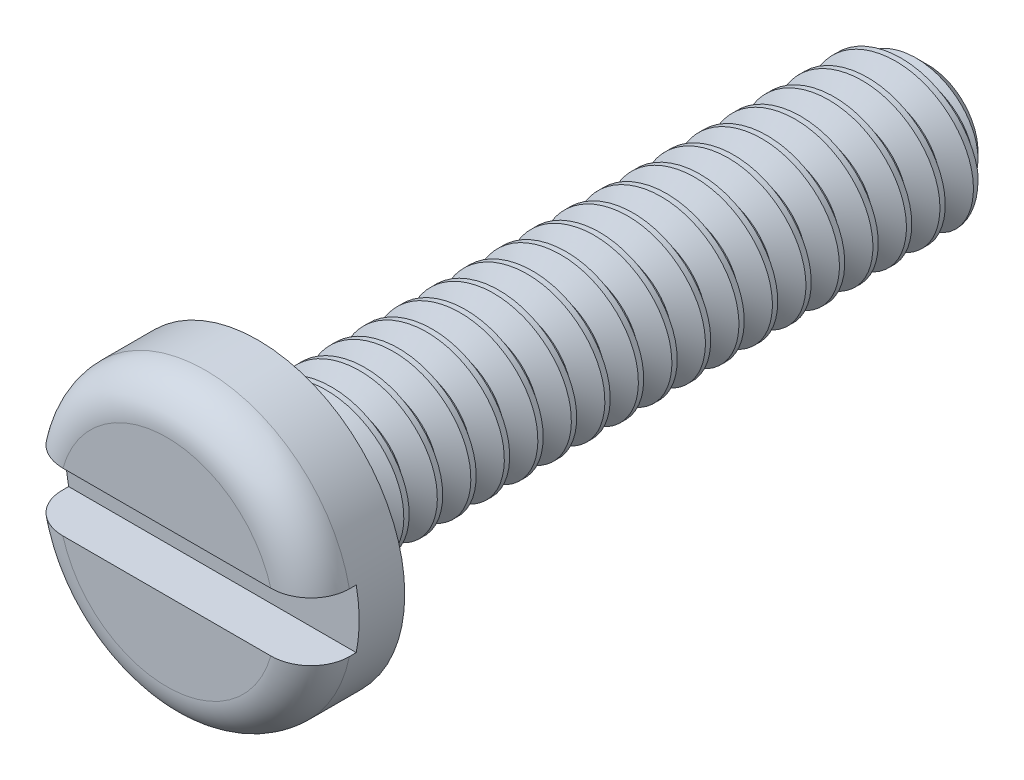
SolidWorks part; units mm, degrees
ref_plane "Front" through (0, 0, 0) normal (0, 0, 1) x (1, 0, 0)
ref_plane "Top" through (0, 0, 0) normal (0, 1, 0) x (1, 0, 0)
ref_plane "Right" through (0, 0, 0) normal (1, 0, 0) x (0, 0, -1)
sketch "Sketch1" plane through (0, 0, 0) normal (0, 0, 1) x (1, 0, 0)
  circle A0 centre (0, 0) radius 2.7813
  dimension "Head Dia" = 5.5626
extrude "Extrude3" add sketch "Sketch1" along normal blind 1.7272
sketch "Sketch11" plane through (0, 0, 0) normal (1, 0, 0) x (0, 0, -1)
  line L0 (0, 0) -> (-1.9812, 0) construction
  line L1 (-1.7272, 2.0472) -> (-1.7272, 0)
  line L4 (-1.7272, 2.7813) -> (-1.7272, -2.7813) construction
  line L5 (-1.9812, 2.8926) -> (0, 2.8926)
  line L7 (0, 2.8926) -> (0, 2.7813)
  line L8 (-0.9931, 2.7813) -> (0, 2.7813)
  line L9 (0, -2.7813) -> (0, 2.7813) construction
  line L11 (0, 2.7813) -> (-1.7272, 2.7813) construction
  line L13 (-1.7272, 0) -> (-1.9812, 0)
  line L14 (-1.9812, 0) -> (-1.9812, 2.8926)
  arc A2 (-1.7272, 2.0472) -> (-0.9931, 2.7813) centre (-0.9931, 2.0472) cw
  dimension "D4" = 0.7341
  dimension "D3" = 0.254
  dimension "D5" = 0.1113
revolve "Cut-Revolve3" cut sketch "Sketch11" angle 360 about L0
sketch "Sketch4" plane through (0, 0, 0) normal (1, 0, 0) x (0, 0, -1)
  line L0 (0, 0) -> (12.7, 0)
  line L3 (12.7, 0) -> (12.7, 1.4224)
  line L4 (12.7, 1.4224) -> (0, 1.4224)
  line L6 (0, 1.4224) -> (0, 0)
  line L9 (12.7, 1.4224) -> (12.7, -1.4224) construction
  dimension "length" = 12.7
  dimension "dia" = 2.8448
revolve "Revolve1" add sketch "Sketch4" angle 360 about L0
sketch "Sketch13" plane through (0, 0, -12.7) normal (0, 0, -1) x (-1, 0, 0)
  circle A2 centre (0, 0) radius 1.4224
curve "Helix/Spiral1" pitch 0.635 height 14.4272 turns 22.72
chamfer "Chamfer2" distance 0.4763 angle 45 1 edges at (1.4224, 0, -12.7)
sketch "Sketch14" plane through (0, 0, 0) normal (1, 0, 0) x (0, 0, -1)
  line L0 (12.7, 1.4422) -> (13.2556, 1.4422)
  line L1 (13.2556, 1.4422) -> (13.0175, 1.0127)
  line L2 (13.0175, 1.0127) -> (12.9381, 1.0127)
  line L3 (12.9381, 1.0127) -> (12.7, 1.4422)
  line L4 (12.8191, 1.2274) -> (13.1366, 1.2274) construction
  dimension "D1" = 0.0794
  dimension "D2" = 58
  dimension "D3" = 0.3175
  dimension "D4" = 0.0198
sweep "Cut-Sweep1" cut profiles "Sketch14" path "Helix/Spiral1"
ref_plane "Plane1" through (0, 0, 25.4) normal (0, 0, -1) x (-1, 0, 0)
sketch "Sketch29" [suppressed] plane through (0, 0, 28.575) normal (0, 0, -1) x (-1, 0, 0)
  circle A0 centre (0, 0) radius 1.7526 construction
  circle A1 centre (0, 0) radius 1.7526
  point P3 (0, -1.7526)
  point P4 (0, 1.7526)
extrude "Extrude11" [suppressed] add sketch "Sketch29" against normal up to surface (28.575 mm away)
sketch "Sketch26" plane through (0, 0, 0) normal (0, 0, 1) x (1, 0, 0)
  circle A1 centre (0, 0) radius 0.5461
  dimension "D1" = 1.0922
extrude "Extrude13" add sketch "Sketch26" along normal up to surface (1.7272 mm away) up to face at (0, 2.0472, 1.7272)
sketch "Sketch31" plane through (0, 0, 1.7272) normal (0, 0, 1) x (1, 0, 0)
  line L0 (-2.7813, 0.5556) -> (2.7813, -0.5556) construction
  line L1 (-2.7813, 0.5556) -> (2.7813, 0.5556)
  line L2 (-2.7813, 0.5556) -> (-2.7813, -0.5556)
  line L3 (-2.7813, -0.5556) -> (2.7813, -0.5556)
  line L4 (2.7813, 0.5556) -> (2.7813, -0.5556)
  circle A0 centre (0, 0) radius 2.7813 construction
  dimension "D1" = 1.1113
extrude "Extrude15" cut sketch "Sketch31" against normal blind 0.8636
sketch "Sketch18" plane through (0, 0, 0) normal (1, 0, 0) x (0, 0, -1)
  line L1 (12.7, 1.4224) -> (0, 1.4224) construction
  point P0 (11.7475, -1.4224)
  point P1 (12.065, 1.4224)
  point P2 (-1.7272, 2.0472)
  dimension "D1" = 0.635
  dimension "D2" = 0.9525
equation "\"D3@Helix/Spiral1\" = \"length@Sketch4\" + \"Head Ht@Extrude3\""
equation "\"D1@Sketch14\" = \"D4@Helix/Spiral1\" * .125"
equation "\"D3@Sketch14\" = \"D4@Helix/Spiral1\" * .5"
equation "\"D5@Sketch11\" = \"Head Dia@Sketch1\" * .02"
equation "\"D4@Sketch14\" = \"D1@Sketch14\" * .25"
equation "\"D1@Chamfer2\" = \"D4@Helix/Spiral1\" * .75"
equation "\"D1@Sketch18\" = \"D4@Helix/Spiral1\""
equation "\"D2@Sketch18\" = \"D4@Helix/Spiral1\" * 1.5"
equation "\"D1@Extrude15\" = \"Head Ht@Extrude3\" * .5"
equation "\"D4@Sketch11\" = \"Head Ht@Extrude3\" * .425"
equation "\"D1@Sketch31\" = \"D4@Helix/Spiral1\" * 1.75"
